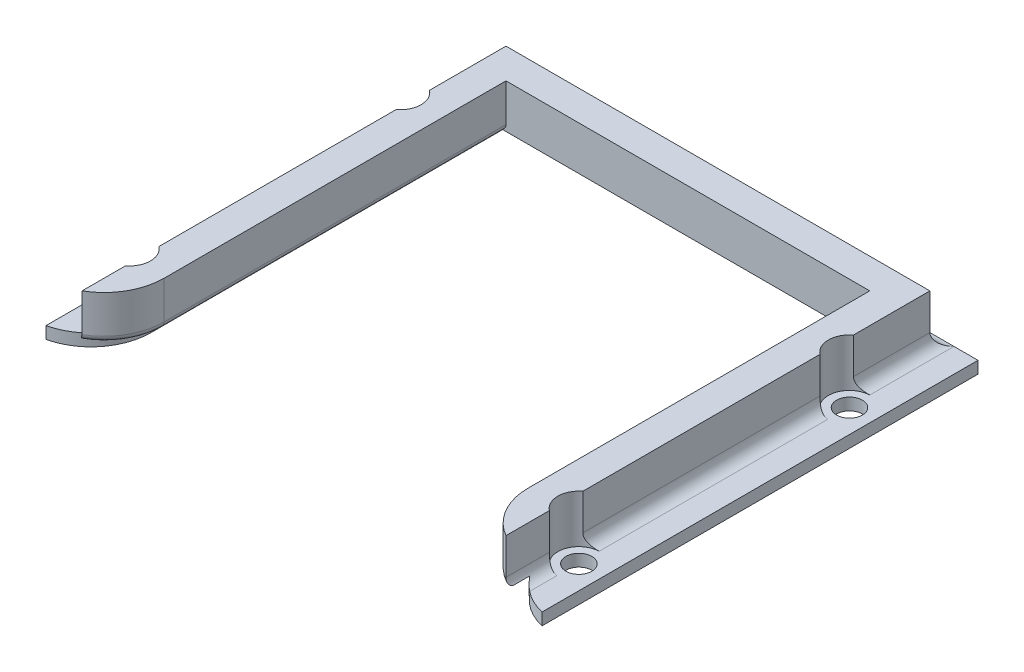
SolidWorks part; units mm, degrees
ref_plane "Front Plane" through (0, 0, 0) normal (0, 0, 1) x (1, 0, 0)
ref_plane "Top Plane" through (0, 0, 0) normal (0, 1, 0) x (1, 0, 0)
ref_plane "Right Plane" through (0, 0, 0) normal (1, 0, 0) x (0, 0, -1)
sketch "Sketch1" plane through (0, 0, 0) normal (0, 1, 0) x (1, 0, 0)
  line L0 (35.25, 35.25) -> (35.25, -35.25)
  line L1 (30.25, 30.25) -> (-30.25, 30.25)
  line L2 (30.25, 30.25) -> (30.25, -30.25)
  line L3 (30.25, -30.25) -> (-30.25, -30.25)
  line L4 (-30.25, 30.25) -> (-30.25, -30.25)
  line L5 (30.25, 30.25) -> (-30.25, -30.25) construction
  line L6 (30.25, -30.25) -> (-30.25, 30.25) construction
  line L7 (35.25, -35.25) -> (-35.25, -35.25)
  line L8 (-35.25, 35.25) -> (-35.25, -35.25)
  line L9 (35.25, 35.25) -> (-35.25, 35.25)
  point P0 (0, 0)
  dimension "D1" = 60.5
  dimension "D2" = 60.5
  dimension "D3" = 5
extrude "Boss-Extrude1" add sketch "Sketch1" along normal blind 10 contours L0 L9 L8 L7 L4 L1 L2 L3 region at (34.253, 0, 0)
sketch "Sketch2" plane through (0, 0, 35.25) normal (0, 0, 1) x (1, 0, 0)
  line L0 (35.25, 0) -> (-35.25, 0) construction
  line L1 (33.5, -2.7) -> (-33.5, -2.7)
  line L2 (33.5, -2.7) -> (33.5, 2.7)
  line L3 (33.5, 2.7) -> (-33.5, 2.7)
  line L4 (-33.5, -2.7) -> (-33.5, 2.7)
  line L5 (33.5, -2.7) -> (-33.5, 2.7) construction
  line L6 (33.5, 2.7) -> (-33.5, -2.7) construction
  point P0 (0, 0)
  dimension "D1" = 2.7
  dimension "D2" = 67
extrude "Cut-Extrude1" cut sketch "Sketch2" against normal blind 70
sketch "Sketch6" plane through (0, 0, 0) normal (0, -1, 0) x (1, 0, 0)
  line L0 (-35.25, -35.25) -> (-35.25, 35.25) construction
  line L1 (41.25, 37.25) -> (-41.25, 37.25)
  line L2 (41.25, 37.25) -> (41.25, -37.25)
  line L3 (41.25, -37.25) -> (-41.25, -37.25)
  line L4 (-41.25, 37.25) -> (-41.25, -37.25)
  line L5 (41.25, 37.25) -> (-41.25, -37.25) construction
  line L6 (41.25, -37.25) -> (-41.25, 37.25) construction
  line L7 (35.25, -35.25) -> (-35.25, -35.25) construction
  line L9 (-35.25, -35.25) -> (35.25, -35.25)
  line L10 (-35.25, -35.25) -> (-35.25, 47.3198)
  line L11 (-35.25, 47.3198) -> (35.25, 47.3198)
  line L12 (35.25, -35.25) -> (35.25, 47.3198)
  point P0 (0, 0)
  line M8 (-35.25, 35.25) -> (-35.25, -35.25)
  line M9 (-35.25, -35.25) -> (35.25, -35.25)
  line M10 (35.25, -35.25) -> (35.25, 35.25)
  dimension "D1" = 6
  dimension "D2" = 2
extrude "Boss-Extrude3" add sketch "Sketch6" against normal blind 2 contours L12 L10 L1 L4 L3 L2 M10 M9 M8 region at (40.1384, 0, 0)
sketch "Sketch7" plane through (0, 2.7, 0) normal (0, -1, 0) x (1, 0, 0)
  line L0 (33.5, 35.25) -> (-33.5, 35.25) construction
  line L1 (-30.25, 30.25) -> (30.25, 30.25)
  line L2 (-30.25, 30.25) -> (-30.25, 35.25)
  line L3 (-30.25, 35.25) -> (30.25, 35.25)
  line L4 (30.25, 30.25) -> (30.25, 35.25)
extrude "Cut-Extrude3" cut sketch "Sketch7" against normal blind 25
fillet "Fillet2" radius 2 3 edges at (35.25, 2, 0) (0, 2, -35.25) (-35.25, 2, 0)
sketch "Sketch8" plane through (0, 0, 37.25) normal (0, 0, 1) x (1, 0, 0)
  line L1 (-54.512, 19.9727) -> (42.871, 19.9727)
  line L2 (-54.512, 19.9727) -> (-54.512, -15.1108)
  line L3 (-54.512, -15.1108) -> (42.871, -15.1108)
  line L4 (42.871, 19.9727) -> (42.871, -15.1108)
extrude "Cut-Extrude4" cut sketch "Sketch8" against normal blind 2 contours L2 L1 L4 L3
sketch "Sketch9" plane through (0, 0, 0) normal (0, -1, 0) x (1, 0, 0)
  line L0 (-33.5, 35.25) -> (-41.25, 35.25) construction
  line L1 (0, -5.5) -> (0, 5.5) construction
  circle A0 centre (-37.375, 25.25) radius 2.15
  circle A1 centre (-37.375, -19.75) radius 2.15
  circle A2 centre (37.375, -19.75) radius 2.15
  circle A3 centre (37.375, 25.25) radius 2.15
  point P6 (0, 0)
  point P7 (-37.375, 35.25)
  dimension "D1" = 4.3
  dimension "D2" = 4.3
  dimension "D3" = 55
  dimension "D4" = 10
extrude "Cut-Extrude5" cut sketch "Sketch9" against normal mid plane 10
sketch "Sketch10" plane through (0, 10, 0) normal (0, 1, 0) x (1, 0, 0)
  line L0 (0, -5.5) -> (0, 5.5) construction
  circle A0 centre (-37.375, 19.75) radius 3.5
  circle A1 centre (-37.375, -25.25) radius 3.5
  circle A2 centre (37.375, -25.25) radius 3.5
  circle A3 centre (37.375, 19.75) radius 3.5
  dimension "D1" = 7
  dimension "D2" = 7
extrude "Cut-Extrude6" cut sketch "Sketch10" against normal blind 8
fillet "Fillet3" radius 10 2 edges at (-33.5, 1.35, 35.25) (33.5, 1.35, 35.25)
fillet "Fillet4" radius 10 2 edges at (30.25, 6.35, 35.25) (-30.25, 6.35, 35.25)
fillet "Fillet5" radius 1 4 edges at (30.25, 2.7, -1.8301) (-30.25, 2.7, -1.8301) (31.5897, 2.7, 31.5897) (-31.5897, 2.7, 31.5897)
